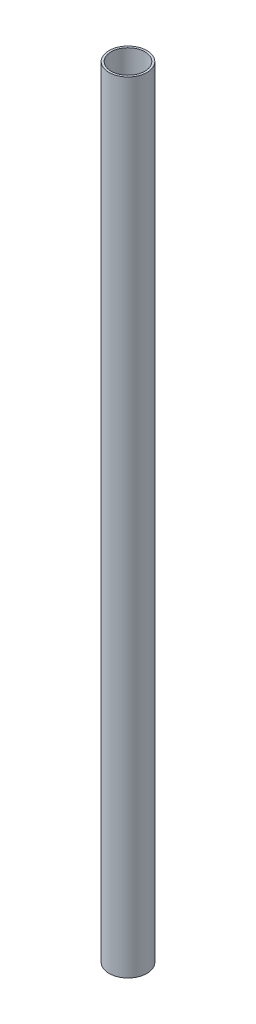
SolidWorks part; units mm, degrees
material "Thornel Mat VMA"
ref_plane "前视基准面" through (0, 0, 0) normal (0, 0, 1) x (1, 0, 0)
ref_plane "上视基准面" through (0, 0, 0) normal (0, 1, 0) x (1, 0, 0)
ref_plane "右视基准面" through (0, 0, 0) normal (1, 0, 0) x (0, 0, -1)
sketch "草图1" plane through (0, 0, 0) normal (0, 1, 0) x (1, 0, 0)
  circle A0 centre (0, 0) radius 9
  circle A1 centre (0, 0) radius 8
  dimension "D1" = 18
  dimension "D2" = 1
extrude "凸台-拉伸2" add sketch "草图1" along normal blind 370
